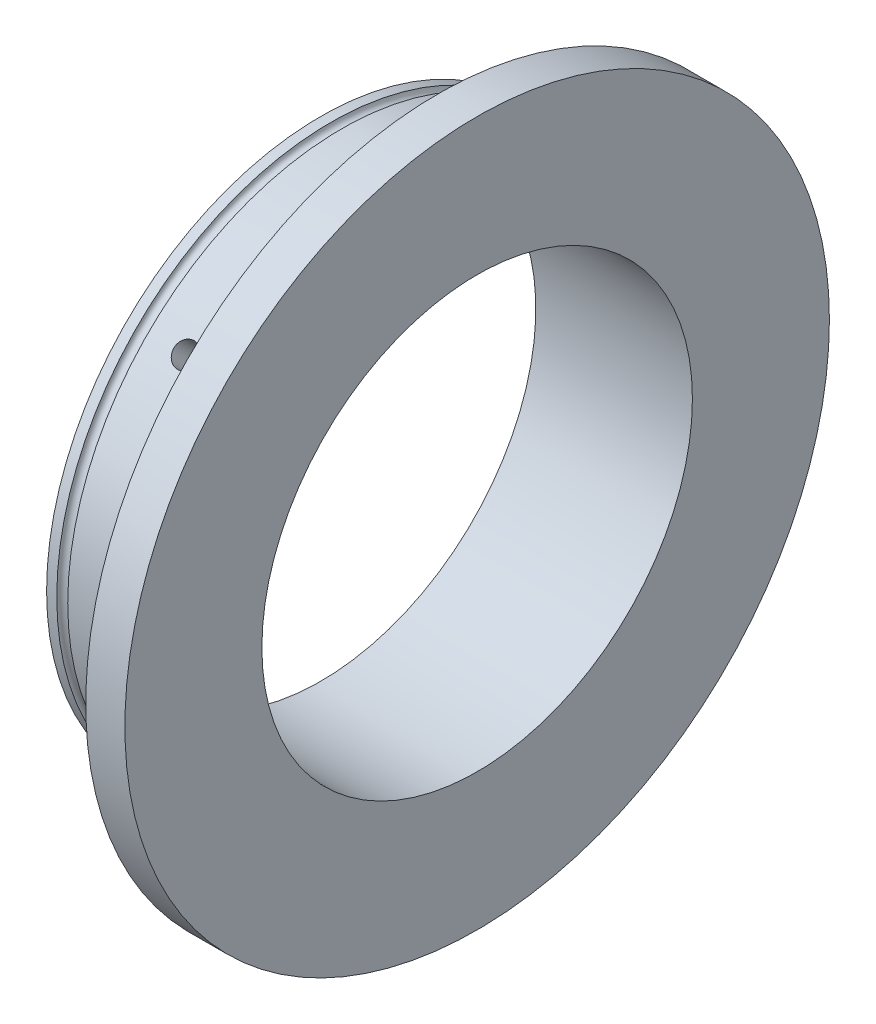
SolidWorks part; units mm, degrees
material "7075-T6 (SN)"
ref_plane "Front Plane" through (0, 0, 0) normal (0, 0, 1) x (1, 0, 0)
ref_plane "Top Plane" through (0, 0, 0) normal (0, 1, 0) x (1, 0, 0)
ref_plane "Right Plane" through (0, 0, 0) normal (1, 0, 0) x (0, 0, -1)
sketch "Sketch1" plane through (0, 0, 0) normal (1, 0, 0) x (0, 0, -1)
  circle A0 centre (0, 0) radius 34.925
  circle A1 centre (0, 0) radius 57.15
  dimension "D1" = 69.85
  dimension "D2" = 114.3
extrude "Boss-Extrude1" add sketch "Sketch1" along normal blind 6.35
sketch "Sketch2" plane through (0, 0, 0) normal (-1, 0, 0) x (0, 0, 1)
  circle A0 centre (0, 0) radius 44.45
  circle A1 centre (0, 0) radius 34.925
  dimension "D1" = 88.9
extrude "Boss-Extrude2" add sketch "Sketch2" along normal blind 19.05
sketch "Sketch3" plane through (0, 0, 0) normal (0, 1, 0) x (1, 0, 0)
  line L0 (0, 44.45) -> (-19.05, 44.45) construction
  line L1 (-19.05, 44.45) -> (-19.05, -44.45) construction
  line L2 (0, 0) -> (-36.7602, 0) construction
  line L3 (0, 57.15) -> (0, -57.15) construction
  circle A0 centre (-16.51, 44.45) radius 0.889
  dimension "D2" = 1.778
  dimension "D1" = 2.54
revolve "Cut-Revolve1" cut sketch "Sketch3" angle 360 about L2
ref_plane "Plane1" through (0, 44.45, 0) normal (0, 1, 0) x (1, 0, 0)
sketch "Sketch4" plane through (0, 44.45, 0) normal (0, 1, 0) x (1, 0, 0)
  line L0 (0, 44.45) -> (0, -44.45) construction
  circle A0 centre (-9.525, 0) radius 1.905
  dimension "D2" = 3.81
  dimension "D1" = 9.525
extrude "Cut-Extrude1" cut sketch "Sketch4" against normal blind 5.08
pattern_circular "CirPattern1" count 8 every 45 about axis through (-19.05, 0, 0) along (1, 0, 0) of "Cut-Extrude1"
